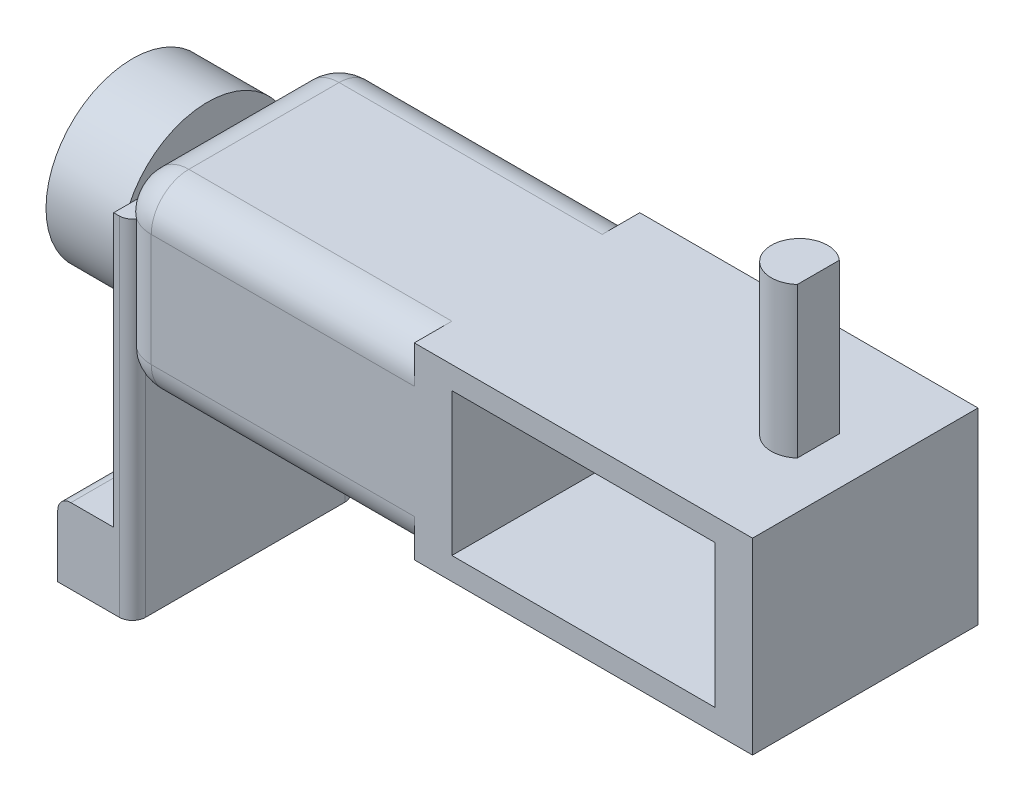
SolidWorks part; units mm, degrees
ref_plane "前视基准面" through (0, 0, 0) normal (0, 0, 1) x (1, 0, 0)
ref_plane "上视基准面" through (0, 0, 0) normal (0, 1, 0) x (1, 0, 0)
ref_plane "右视基准面" through (0, 0, 0) normal (1, 0, 0) x (0, 0, -1)
sketch "草图1" plane through (0, 0, 0) normal (0, 0, 1) x (1, 0, 0)
  line L1 (0, 0) -> (16, 0)
  line L2 (0, 0) -> (0, 10)
  line L3 (0, 10) -> (16, 10)
  line L4 (16, 0) -> (16, 10)
  line L5 (16, 10) -> (34, 10)
  line L6 (16, 10) -> (16, 8.5)
  line L7 (16, 8.5) -> (34, 8.5)
  line L8 (34, 10) -> (34, 8.5)
  line L9 (16, 0) -> (34, 0)
  line L10 (16, 0) -> (16, 1.5)
  line L11 (16, 1.5) -> (34, 1.5)
  line L12 (34, 0) -> (34, 1.5)
  line L13 (34, 1.5) -> (32, 1.5)
  line L14 (34, 1.5) -> (34, 8.5)
  line L15 (34, 8.5) -> (32, 8.5)
  line L16 (32, 1.5) -> (32, 8.5)
  dimension "D1" = 16
  dimension "D2" = 34
  dimension "D3" = 2
  dimension "D4" = 10
  dimension "D5" = 1.5
  dimension "D6" = 1.5
extrude "凸台-拉伸2" add sketch "草图1" along normal blind 12 contours L1 L4 L3 L2 region at (8, 5, 0)
fillet "圆角1" radius 2 4 edges at (8, 0, 0) (8, 0, 12) (8, 10, 12) (8, 10, 0)
fillet "圆角2" radius 2 8 edges at (0, 9.4142, 0.5858) (0, 10, 6) (0, 9.4142, 11.4142) (0, 5, 12) (0, 0.5858, 11.4142) (0, 0, 6) (0, 0.5858, 0.5858) (0, 5, 0)
sketch "草图2" plane through (0, 0, 12) normal (0, 0, 1) x (1, 0, 0)
  line L1 (16, 10) -> (32, 10)
  line L2 (16, 10) -> (16, 8.8)
  line L3 (16, 8.8) -> (32, 8.8)
  line L4 (16, 8) -> (2, 8)
  line L5 (2, 8) -> (2, 2)
  line L6 (2, 2) -> (16, 2)
  line L7 (16, 2) -> (16, 8)
  line L8 (16, 8) -> (2, 8)
  line L9 (2, 8) -> (2, 2)
  line L10 (2, 2) -> (16, 2)
  line L11 (16, 2) -> (16, 8)
  line L12 (16, 10) -> (2, 10)
  line L13 (2, 10) -> (2, 8)
  line L14 (2, 8) -> (16, 8)
  line L15 (16, 8) -> (16, 10)
  line L16 (16, 10) -> (2, 10)
  line L17 (2, 10) -> (2, 8)
  line L18 (2, 8) -> (16, 8)
  line L19 (16, 8) -> (16, 10)
  line L20 (16, 2) -> (2, 2)
  line L21 (2, 2) -> (2, 0)
  line L22 (2, 0) -> (16, 0)
  line L23 (16, 0) -> (16, 2)
  line L24 (16, 2) -> (2, 2)
  line L25 (2, 2) -> (2, 0)
  line L26 (2, 0) -> (16, 0)
  line L27 (16, 0) -> (16, 2)
  line L28 (32, 10) -> (32, 8.8)
  line L29 (16, 0) -> (32, 0)
  line L30 (16, 0) -> (16, 1.2)
  line L31 (16, 1.2) -> (32, 1.2)
  line L32 (32, 0) -> (32, 1.2)
  line L33 (32, 0) -> (34, 0)
  line L34 (32, 0) -> (32, 10)
  line L35 (32, 10) -> (34, 10)
  line L36 (34, 0) -> (34, 10)
  line L37 (18, 1.2) -> (16, 1.2)
  line L38 (18, 1.2) -> (18, 8.8)
  line L39 (18, 8.8) -> (16, 8.8)
  line L40 (16, 1.2) -> (16, 8.8)
  line M23 (16, 2) -> (16, 8)
  dimension "D4" = 1.2
  dimension "D5" = 1.2
  dimension "D6" = 2
  dimension "D7" = 18
  dimension "D8" = 2
  dimension "D1" = 0
  dimension "D2" = 0
  dimension "D3" = 0
extrude "凸台-拉伸3" add sketch "草图2" against normal blind 12 contours L31 L38 L3 L19 L27 M23 | L28 L1 L2 L3 | L29 L32 L31 L27 | L33 L36 L35 L28 L34 L32 region at (24, 9.4, 12) region at (33, 5, 12) region at (17, 5, 12) region at (24, 0.6, 12)
sketch "草图3" plane through (0, 0, 0) normal (-1, 0, 0) x (0, 0, 1)
  line L0 (2, 8) -> (10, 2) construction
  line L4 (10, 2) -> (10, 8)
  line L5 (10, 8) -> (2, 8)
  line L6 (2, 8) -> (2, 2)
  line L7 (2, 2) -> (10, 2)
  line L8 (10, 2) -> (10, 8)
  line L9 (10, 8) -> (2, 8)
  line L10 (2, 8) -> (2, 2)
  line L11 (2, 2) -> (10, 2)
  circle A0 centre (6, 5) radius 4.6
  point P6 (6, 5)
  dimension "D2" = 9.2
  dimension "D1" = 0
extrude "凸台-拉伸6" add sketch "草图3" along normal blind 5 contours L0 A0 L10 L11 | A0 L0 L8 L9 | L9 A0 | L11 A0 | L10 A0 | L8 A0 region at (0, 5.9996, 7.3157) region at (0, 4.0004, 4.6843) region at (0, 8.6506, 6) region at (0, 5, 1.7586) region at (0, 1.3494, 6) region at (0, 5, 10.2414)
sketch "草图5" plane through (0, 0, 0) normal (1, 0, 0) x (0, 0, -1)
  line L1 (-9.4871, 8) -> (-2.5129, 8)
  line L2 (-9.4871, 8) -> (-2.5129, 8)
  circle A0 centre (-6, 5) radius 4.6
  arc A1 (-2.5129, 8) -> (-9.4871, 8) centre (-6, 5) ccw
  arc A2 (-2.5129, 8) -> (-9.4871, 8) centre (-6, 5) ccw
  circle A3 centre (-6, 5) radius 0.9757
  line M3 (-9.4871, 8) -> (-2.5129, 8)
  arc M4 (-2.5129, 8) -> (-9.4871, 8) centre (-6, 5) ccw
  dimension "D1" = 0
extrude "切除-拉伸4" cut sketch "草图5" against normal blind 1 contours A0 A3 M3 | M4 M3 region at (0, 8.6506, 6) region at (0, 7.8807, 6)
sketch "草图6" plane through (0, 0, 0) normal (-1, 0, 0) x (0, 0, 1)
  line L1 (0, 2) -> (12, 2)
  line L2 (0, 2) -> (0, -10.5)
  line L3 (0, -10.5) -> (12, -10.5)
  line L4 (10, 8) -> (2, 8)
  line L5 (2, 8) -> (2, 2)
  line L6 (2, 2) -> (10, 2)
  line L7 (10, 2) -> (10, 8)
  line L8 (10, 8) -> (2, 8)
  line L9 (2, 8) -> (2, 2)
  line L10 (2, 2) -> (10, 2)
  line L11 (10, 2) -> (10, 8)
  line L12 (0, 2) -> (2, 2)
  line L13 (2, 2) -> (2, 8)
  line L14 (2, 8) -> (0, 8)
  line L15 (0, 8) -> (0, 2)
  line L16 (0, 2) -> (2, 2)
  line L17 (2, 2) -> (2, 8)
  line L18 (2, 8) -> (0, 8)
  line L19 (0, 8) -> (0, 2)
  line L20 (10, 2) -> (12, 2)
  line L21 (12, 2) -> (12, 8)
  line L22 (12, 8) -> (10, 8)
  line L23 (10, 8) -> (10, 2)
  line L24 (10, 2) -> (12, 2)
  line L25 (12, 2) -> (12, 8)
  line L26 (12, 8) -> (10, 8)
  line L27 (10, 8) -> (10, 2)
  line L28 (12, 2) -> (12, -10.5)
  line M17 (10, 8) -> (2, 8)
  line M18 (2, 8) -> (2, 2)
  line M19 (2, 2) -> (10, 2)
  line M20 (10, 2) -> (10, 8)
  circle M21 centre (6, 5) radius 0.9757
  dimension "D4" = 18.5
  dimension "D1" = 0
  dimension "D2" = 0
  dimension "D3" = 0
extrude "凸台-拉伸7" add sketch "草图6" against normal blind 1 contours L28 L1 L2 L3 M19 | L18 L19 L1 M18 | L25 L26 L1 M20 | M20 M17 M18 M19 M21 region at (0, 5, 1) region at (0, -4.25, 6) region at (0, 5, 2.1) region at (0, 5, 11)
sketch "草图7" plane through (0, -10.5, 0) normal (0, -1, 0) x (1, 0, 0)
  line L1 (0, 0) -> (-2.9752, 0)
  line L2 (0, 0) -> (0, 12)
  line L3 (0, 12) -> (-2.9752, 12)
  line L4 (0, 12) -> (0, 0)
  line L5 (0, 0) -> (1, 0)
  line L6 (1, 0) -> (1, 12)
  line L7 (1, 12) -> (0, 12)
  line L8 (0, 12) -> (0, 0)
  line L9 (0, 0) -> (1, 0)
  line L10 (1, 0) -> (1, 12)
  line L11 (1, 12) -> (0, 12)
  line L12 (-2.9752, 0) -> (-2.9752, 12)
  line M9 (0, 12) -> (0, 0)
  dimension "D1" = 0
extrude "凸台-拉伸8" add sketch "草图7" against normal blind 4 contours L12 L1 L3 M9 region at (-1.4876, -10.5, 6)
fillet "圆角3" radius 0.7 3 edges at (1, -1.25, 12) (1, -1.25, 0) (-2.9752, -6.5, 6)
sketch "草图9" plane through (0, 10, 0) normal (0, 1, 0) x (1, 0, 0)
  line L0 (0, -6) -> (34, -6) construction
  line L1 (31.5, -4.882) -> (31.5, -7.118)
  line L4 (0, -10) -> (2, -10)
  line L5 (2, -10) -> (2, -2)
  line L6 (2, -2) -> (0, -2)
  line L7 (0, -2) -> (0, -10)
  line L8 (16, -2) -> (2, -2)
  line L9 (2, -2) -> (2, -10)
  line L10 (2, -10) -> (16, -10)
  line L11 (16, -10) -> (16, -12)
  line L12 (16, -12) -> (34, -12)
  line L13 (34, -12) -> (34, 0)
  line L14 (34, 0) -> (16, 0)
  line L15 (16, 0) -> (16, -2)
  line L16 (16, -2) -> (2, -2)
  line L17 (2, -2) -> (2, -10)
  line L18 (2, -10) -> (16, -10)
  line L19 (16, -10) -> (16, -12)
  line L20 (16, -12) -> (34, -12)
  line L21 (34, -12) -> (34, 0)
  line L22 (34, 0) -> (16, 0)
  line L23 (16, 0) -> (16, -2)
  line L24 (0, -10) -> (2, -10)
  line L25 (2, -10) -> (2, -2)
  line L26 (2, -2) -> (0, -2)
  line L27 (0, -2) -> (0, -10)
  circle A0 centre (30.5, -6) radius 1.5
  dimension "D4" = 3
  dimension "D3" = 34
  dimension "D5" = 3.5
  dimension "D6" = 1
  dimension "D1" = 0
  dimension "D2" = 0
extrude "凸台-拉伸9" add sketch "草图9" along normal blind 8 contours L0 A0 L1 | A0 L0 L1 region at (30.352, 10, 6.662) region at (30.352, 10, 5.338)
